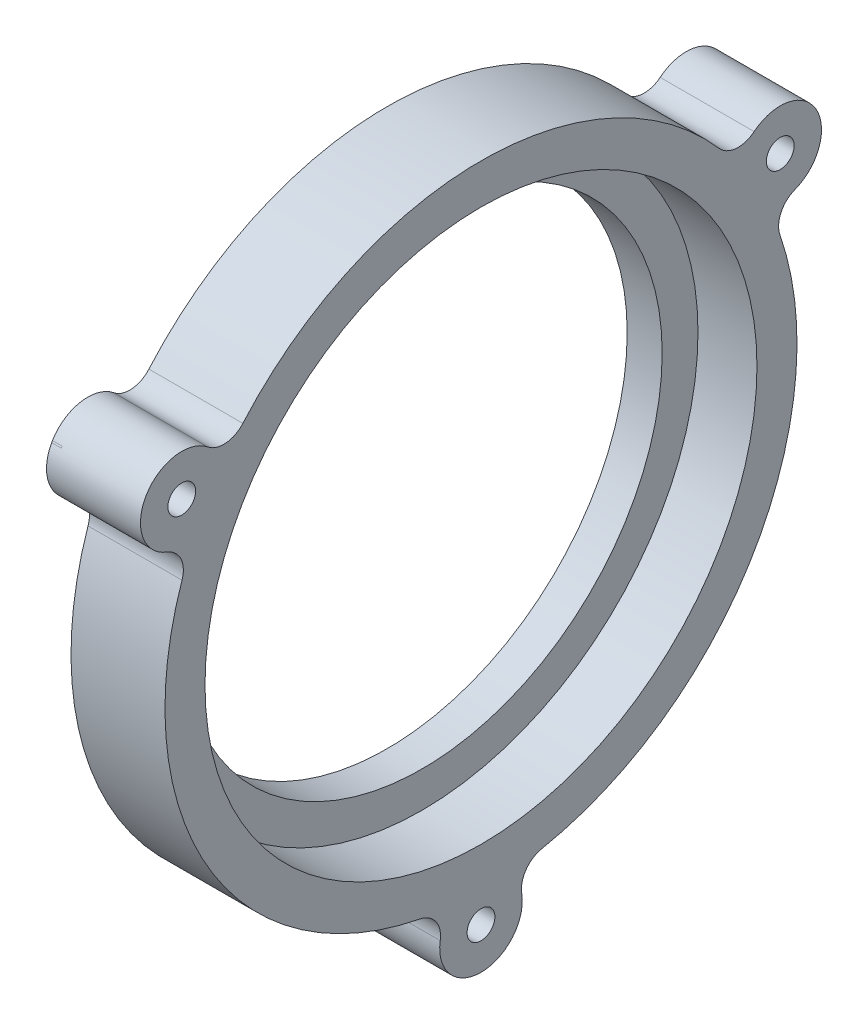
SolidWorks part; units mm, degrees
ref_plane "Plane1" through (0, 0, 0) normal (0, 0, 1) x (1, 0, 0)
ref_plane "Plane2" through (0, 0, 0) normal (0, 1, 0) x (1, 0, 0)
ref_plane "Plane3" through (0, 0, 0) normal (1, 0, 0) x (0, 0, -1)
sketch "HoldingSke" plane through (0, 0, 0) normal (0, 1, 0) x (1, 0, 0)
  line L0 (0, 0) -> (0.4589, -0.6553)
  line L1 (-15, 0) -> (100, 0) construction
  line L2 (0, 0) -> (-2.1039, 2.3779)
  line L3 (0, 0) -> (-11.863, 4.5341)
  line L4 (0, 0) -> (4.9534, 7.0742)
  line L5 (0, 0) -> (-23.7986, -8.8762)
  line L6 (0, 0) -> (-10.5278, -7.1032)
  line L7 (-2.1039, 2.3779) -> (3.3635, 27.1825)
  line L8 (-76.2, 3.6279) -> (-54.61, 3.6279)
  line L9 (-67.7845, 28.3722) -> (-49.3413, 33.142)
  line L10 (-76.2, 71.12) -> (104.1128, 71.12)
  line L11 (0, 0) -> (-26, 0)
  line L12 (-76.2, 101.6) -> (-76.155, 101.6)
  line L13 (24.9733, 27.94) -> (52.9518, 28.4284)
  line L14 (24.9733, 27.94) -> (24.9743, 27.94)
  line L15 (24.9733, 27.94) -> (100.4006, 29.5858)
  circle A0 centre (0, 0) radius 37.5
  circle A1 centre (0, 0) radius 12.7
  circle A2 centre (0, 0) radius 12.7
  dimension "MHD" = 25.4
  dimension "Hub_dia" = 25.4
  dimension "Diameter" = 75
  dimension "Num_teeth" = 55
  dimension "Pitch" = 0.8
  dimension "Overall_len" = 25.4
  dimension "Show_teeth" = 55
  dimension "Thickness" = 12.7
  dimension "OAL" = 25.4001
  dimension "T_dim" = 21.59
  dimension "Ap" = 14.5
  dimension "H" = 19.05
  dimension "Pitch_radius" = 180.3128
  dimension "Width" = 26
  dimension "Backlash" = 0.045
  dimension "Addendum_fac" = 1
  dimension "Dedendum_fac" = 1.25
  dimension "Clearance_fac" = 0.25
  dimension "Dedendum_add" = 0.001
  dimension "Module" = 1.25
sketch "BasProSke" plane through (0, 0, 0) normal (0, 1, 0) x (1, 0, 0)
  line L0 (-10, 0) -> (60, 0) construction
  line L1 (0, 33.125) -> (0, 37.5)
  line L2 (0, 33.125) -> (26, 33.125)
  line L3 (26, 33.125) -> (26, 37.5)
  line L4 (26, 37.5) -> (0, 37.5)
  dimension "Diameter" = 75
  dimension "Thickness" = 26
  dimension "Inside_diameter" = 66.25
revolve "Base-Revolve" add sketch "BasProSke" angle 360 about L0
sketch "TooCutSke" plane through (0, 0, 0) normal (1, 0, 0) x (0, 0, -1)
  line L3 (1.0941, 34.3576) -> (1.0941, 53.6633) construction
  line L4 (0, 0) -> (0, 59.563) construction
  line L5 (0, 0) -> (-3.9007, 68.2161) construction
  line L6 (-15.2783, 29.1274) -> (36.0712, 32.0636) construction
  circle A0 centre (0, 0) radius 34.375 construction
  circle A1 centre (0, 0) radius 35.9385 construction
  circle A2 centre (0, 0) radius 29.9521 construction
  circle A3 centre (0, 0) radius 33.0996 construction
  arc A4 (1.4514, 33.0678) -> (0.5036, 35.935) centre (-15.2783, 29.1274) ccw
  arc A5 (1.4514, 33.0678) -> (-1.4514, 33.0678) centre (0, 0) ccw
  arc A6 (0.5036, 35.935) -> (-0.5036, 35.935) centre (0, 0) ccw
  arc A7 (-0.5036, 35.935) -> (-1.4514, 33.0678) centre (15.2783, 29.1274) ccw
  dimension "Pitch_dia" = 68.75
  dimension "Base_dia" = 59.9041
  dimension "Root_dia" = 71.877
  dimension "Overcut_dia" = 66.1992
  dimension "Flank_rad" = 17.1875
  dimension "Half_ang" = 3.273
  dimension "Half_CT" = 1.0941
extrude "ToothCut" cut sketch "TooCutSke" along normal through all
fillet "Breaks" [suppressed] radius 0.125
fillet "RootFillets" [suppressed] radius 0.3135
pattern_circular "TeethCuts" count 55 every 6.545 about axis through (-10, 0, 0) along (1, 0, 0) of "RootFillets", "Breaks", "ToothCut"
sketch "Sketch2" plane through (0, 0, 0) normal (-1, 0, 0) x (0, 0, 1)
  circle A0 centre (0, 0) radius 37.5
extrude "Boss-Extrude2" add sketch "Sketch2" along normal blind 4.5
sketch "Sketch3" plane through (-4.5, 0, 0) normal (-1, 0, 0) x (0, 0, 1)
  line L0 (0, 0) -> (0, 8.5) construction
  line L1 (0, 0) -> (7.536, 0) construction
  circle A0 centre (0, 0) radius 2.25
  circle A1 centre (0, 8.5) radius 1.8
  circle A2 centre (0, -8.5) radius 1.8
  dimension "D1" = 4.5
  dimension "D2" = 3.6
extrude "Cut-Extrude1" cut sketch "Sketch3" against normal blind 4.5
sketch "Sketch4" plane through (0, 0, 0) normal (1, 0, 0) x (0, 0, -1)
  circle A0 centre (0, -8.5) radius 3.25
  circle A1 centre (0, 8.5) radius 3.25
  dimension "D1" = 6.5
extrude "Cut-Extrude2" cut sketch "Sketch4" against normal blind 3
sketch "Sketch5" plane through (26, 0, 0) normal (1, 0, 0) x (0, 0, -1)
  circle A0 centre (0, 0) radius 37.5
  circle A1 centre (0, 0) radius 28.5
  dimension "D1" = 57
extrude "Boss-Extrude3" add sketch "Sketch5" along normal blind 4
sketch "Sketch6" plane through (30, 0, 0) normal (1, 0, 0) x (0, 0, -1)
  circle A0 centre (0, 0) radius 37.5
  circle A1 centre (0, 0) radius 32.75
  dimension "D1" = 65.5
extrude "Boss-Extrude4" add sketch "Sketch6" along normal blind 7
sketch "Sketch7" plane through (37, 0, 0) normal (1, 0, 0) x (0, 0, -1)
  line L0 (0, 0) -> (0, -41) construction
  line L1 (0, 0) -> (0, -45.9) construction
  circle A0 centre (0, -41) radius 1.65
  circle A1 centre (-35.507, 20.5) radius 1.65
  circle A2 centre (35.507, 20.5) radius 1.65
  arc A4 (3.2765, -37.3566) -> (-3.2765, -37.3566) centre (0, -41) cw
  arc A5 (-33.99, 15.8408) -> (-30.7135, 21.5158) centre (-35.507, 20.5) cw
  arc A6 (30.7135, 21.5158) -> (33.99, 15.8408) centre (35.507, 20.5) cw
  circle A7 centre (0, 0) radius 37.5
  point P10 (0, 0)
  point P22 (0, 0)
  point P23 (0, 0)
  dimension "D2" = 3.3
  dimension "D5" = 45.9
  dimension "D1" = 41
  dimension "D4" = 3
  dimension "D3" = 3
extrude "Boss-Extrude5" add sketch "Sketch7" against normal blind 10
fillet "Fillet1" radius 3 6 edges at (32, 21.5158, 30.7135) (32, 15.8408, 33.99) (32, -37.3566, 3.2765) (32, -37.3566, -3.2765) (32, 15.8408, -33.99) (32, 21.5158, -30.7135)
sketch "Sketch8" plane through (-4.5, 0, 0) normal (-1, 0, 0) x (0, 0, 1)
  line L0 (0, 0) -> (0, 41) construction
  line L1 (0, 41) -> (0, 45.9) construction
  circle A2 centre (-35.507, -20.5) radius 1.65
  circle A3 centre (0, 41) radius 1.65
  arc A4 (-3.278, 37.3557) -> (3.275, 37.3557) centre (-0.0015, 40.9991) cw
  circle A5 centre (0, 0) radius 37.5
  circle A6 centre (0.0015, 0.0009) radius 37.5
  circle A7 centre (35.507, -20.5) radius 1.65
  circle A8 centre (0.0015, -0.0009) radius 37.5
  arc A9 (-30.712, -21.5167) -> (-33.9885, -15.8416) centre (-35.5055, -20.5009) cw
  arc A10 (33.99, -15.839) -> (30.7135, -21.5141) centre (35.507, -20.4983) cw
  point P13 (0, 0)
  point P28 (0.001, 0)
  point P29 (0, 0)
  dimension "D2" = 3
  dimension "D1" = 41
  dimension "D4" = 3
extrude "Boss-Extrude6" add sketch "Sketch8" against normal blind 10
fillet "Fillet2" radius 3 2 edges at (0.5, -15.8412, -33.9898) (0.5, -21.5177, -30.7122)
sketch "Sketch9" plane through (-4.5, 0, 0) normal (-1, 0, 0) x (0, 0, 1)
  circle A0 centre (0, 0) radius 37.6
  circle A1 centre (0, 0) radius 37.5
extrude "Boss-Extrude7" add sketch "Sketch9" against normal blind 10
fillet "Fillet3" radius 3 4 edges at (0.5, 37.4482, 3.375) (0.5, 37.448, -3.3778) (0.5, -15.7987, 34.1198) (0.5, -21.647, 30.7436)
sketch "Sketch10" plane through (-4.5, 0, 0) normal (-1, 0, 0) x (0, 0, 1)
  circle A1 centre (0, 0) radius 2.25
  circle A2 centre (0, 0) radius 45.8991
extrude "Cut-Extrude3" cut sketch "Sketch10" against normal up to surface (31.5 mm away) up to face at (27, 19.9317, -34.5228)
sketch "Sketch12" plane through (27, 0, 0) normal (-1, 0, 0) x (0, 0, 1)
  arc A0 (-37.25, 15.9205) -> (-32.4125, 24.2992) centre (-35.507, 20.5) cw
  arc A1 (-32.4125, 24.2992) -> (-39.701, 23.0339) centre (-35.507, 20.5) ccw construction
  arc A2 (-32.2756, 24.1941) -> (-28.2574, 24.653) centre (-30.5179, 26.6253) ccw
  arc A3 (-32.4125, 24.2992) -> (-28.2574, 24.653) centre (-30.5179, 26.6253) ccw construction
  arc A4 (-35.4788, 12.1451) -> (-37.25, 15.9205) centre (-38.3171, 13.1167) ccw
  arc A5 (32.4125, 24.2992) -> (28.2574, 24.653) centre (30.5179, 26.6253) cw
  arc A7 (39.701, 23.0339) -> (32.4125, 24.2992) centre (35.507, 20.5) ccw construction
  arc A8 (32.4125, 24.2992) -> (37.25, 15.9205) centre (35.507, 20.5) cw
  arc A9 (37.25, 15.9205) -> (35.4788, 12.1451) centre (38.3171, 13.1167) ccw construction
  arc A10 (37.25, 15.9205) -> (35.4788, 12.1451) centre (38.3171, 13.1167) ccw
  arc A11 (7.2215, -36.7981) -> (35.4788, 12.1451) centre (0, 0) ccw construction
  arc A12 (-4.8375, -40.2197) -> (4.8375, -40.2197) centre (0, -41) ccw
  arc A14 (7.2215, -36.7981) -> (4.8375, -40.2197) centre (7.7992, -39.742) ccw construction
  arc A16 (4.8375, -40.2197) -> (7.2215, -36.7981) centre (7.7992, -39.742) cw
  arc A17 (-4.8375, -40.2197) -> (-7.2215, -36.7981) centre (-7.7992, -39.742) ccw
  arc A18 (-4.8375, -40.2197) -> (-7.2215, -36.7981) centre (-7.7992, -39.742) ccw construction
  arc A19 (-7.2215, -36.7981) -> (-35.4788, 12.1451) centre (0, 0) cw
  arc A20 (-35.4788, 12.1451) -> (-37.25, 15.9205) centre (-38.3171, 13.1167) ccw construction
  arc A21 (-28.2574, 24.653) -> (28.2574, 24.653) centre (0, 0) cw
  arc A22 (28.2574, 24.653) -> (-28.2574, 24.653) centre (0, 0) ccw construction
  arc A23 (28.2574, 24.653) -> (32.4125, 24.2992) centre (30.5179, 26.6253) ccw construction
  circle A24 centre (0, 0) radius 28.5
extrude "Boss-Extrude8" add sketch "Sketch12" along normal blind 1.15
equation "' \"Module@HoldingSke\" = 6.35"
equation "' \"Num_teeth@HoldingSke\" = 24"
equation "' \"Ap@HoldingSke\" =  14.5"
equation "' \"Ap@HoldingSke\" = 14.5"
equation "' \"Width@HoldingSke\" = 12"
equation "' \"Diameter@HoldingSke\" = 8 * 25.4"
equation "' \"Show_teeth@HoldingSke\" = 100"
equation "' \"Backlash@HoldingSke\" = 0.009 * 25.4"
equation "' \"Addendum_fac@HoldingSke\" = 1.0"
equation "' \"Dedendum_fac@HoldingSke\" = 1.25"
equation "' \"Dedendum_add@HoldingSke\" = 0.00005 * 25.4"
equation "' \"Clearance_fac@HoldingSke\" = 0.25"
equation "\"Pitch@HoldingSke\" = 1 / \"Module@HoldingSke\" "
equation "\"Overcut_dia@TooCutSke\" = (\"Num_teeth@HoldingSke\" - 2 * \"Addendum_fac@HoldingSke\") / \"Pitch@HoldingSke\" - 0.002 * 25.4"
equation "\"Pitch_dia@TooCutSke\" = \"Num_teeth@HoldingSke\" / \"Pitch@HoldingSke\""
equation "\"Base_dia@TooCutSke\" = \"Num_teeth@HoldingSke\" / \"Pitch@HoldingSke\" * cos((\"Ap@HoldingSke\"  * 3.14159265 / 180)) * 0.90"
equation "\"Root_dia@TooCutSke\" = \"Num_teeth@HoldingSke\"  / \"Pitch@HoldingSke\" + 2 *  \"Dedendum_fac@HoldingSke\"/ \"Pitch@HoldingSke\" + \"Dedendum_add@HoldingSke\" * 2"
equation "\"Half_ang@TooCutSke\" = 180 / \"Num_teeth@HoldingSke\""
equation "\"Half_CT@TooCutSke\" = \"Num_teeth@HoldingSke\" / \"Pitch@HoldingSke\" * sin((3.14159265 / 2 / \"Num_teeth@HoldingSke\")) / 2 + 10 * \"Backlash@HoldingSke\" / 4"
equation "\"Flank_rad@TooCutSke\" = \"Num_teeth@HoldingSke\" / \"Pitch@HoldingSke\" / 4"
equation "\"Radius@RootFillets\"= \"Clearance_fac@HoldingSke\" / \"Pitch@HoldingSke\" + \"Dedendum_add@HoldingSke\""
equation "\"Break_rad@Breaks\" = 0.02 / \"Pitch@HoldingSke\" * 5"
equation "\"Num_teeth@TeethCuts\" = int( \"Show_teeth@HoldingSke\" ) + 1"
equation "\"Num_teeth@TeethCuts\" = ((sgn( \"Num_teeth@TeethCuts\" - \"Num_teeth@HoldingSke\" )-1)*( \"Num_teeth@TeethCuts\" - \"Num_teeth@HoldingSke\" ))/-2+ \"Num_teeth@HoldingSke\""
equation "\"Num_teeth@TeethCuts\" = ((sgn( \"Num_teeth@TeethCuts\" - 2.0)+1)*( \"Num_teeth@TeethCuts\" - 2.0))/2 +2.0"
equation "\"Angle@TeethCuts\" = 360.0 / \"Num_teeth@HoldingSke\""
equation "\"Diameter@BasProSke\" = \"Num_teeth@HoldingSke\"  / \"Pitch@HoldingSke\" + 2 *  \"Dedendum_fac@HoldingSke\"/ \"Pitch@HoldingSke\" + \"Dedendum_add@HoldingSke\" * 2 + 0.002 * 25.4"
equation "\"Diameter@BasProSke\" = ((sgn( \"Diameter@BasProSke\"  - \"Diameter@HoldingSke\" )+1)*( \"Diameter@BasProSke\"  - \"Diameter@HoldingSke\" ))/2 + \"Diameter@HoldingSke\""
equation "\"Inside_diameter@BasProSke\" =  (\"Num_teeth@HoldingSke\" - 2 * \"Addendum_fac@HoldingSke\") / \"Pitch@HoldingSke\" "
equation "\"Thickness@BasProSke\"  = \"Width@HoldingSke\""
